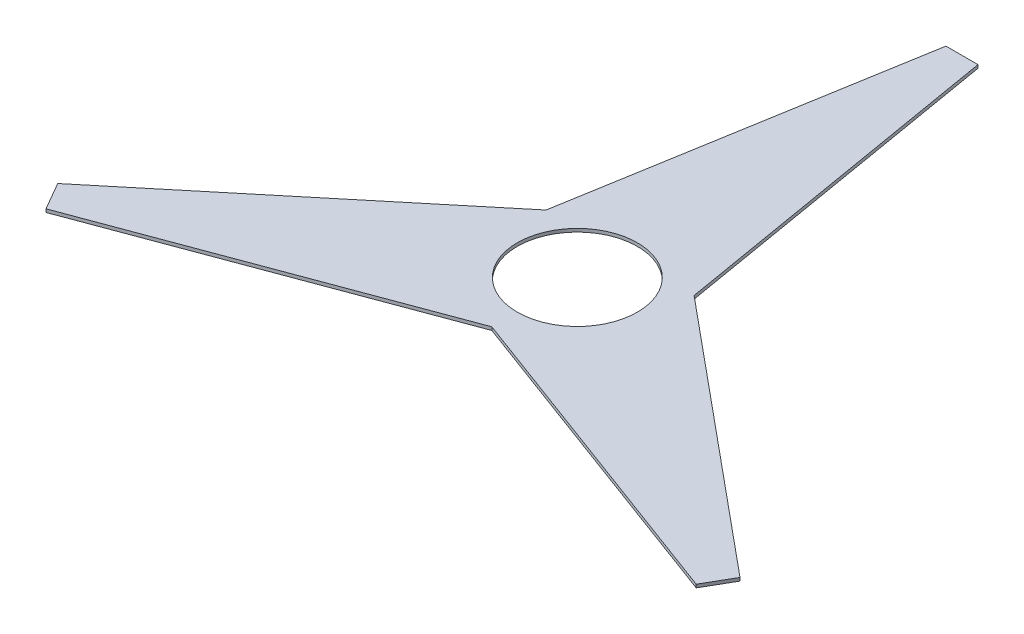
SolidWorks part; units mm, degrees
ref_plane "Alzado" through (0, 0, 0) normal (0, 0, 1) x (1, 0, 0)
ref_plane "Planta" through (0, 0, 0) normal (0, 1, 0) x (1, 0, 0)
ref_plane "Vista lateral" through (0, 0, 0) normal (1, 0, 0) x (0, 0, -1)
sketch "Croquis1" plane through (0, 0, 0) normal (0, 1, 0) x (1, 0, 0)
  line L0 (0, 0) -> (0, 1200) construction
  line L1 (1064.2305, -556.6987) -> (230.9516, 133.34)
  line L2 (1014.2305, -643.3013) -> (0, -266.68)
  line L6 (-50, 1200) -> (-230.9516, 133.34)
  line L7 (50, 1200) -> (230.9516, 133.34)
  line L9 (-1014.2305, -643.3013) -> (0, -266.68)
  line L10 (-1064.2305, -556.6987) -> (-230.9516, 133.34)
  line L11 (-50, 1200) -> (50, 1200)
  line L12 (1064.2305, -556.6987) -> (1014.2305, -643.3013)
  line L13 (-1064.2305, -556.6987) -> (-1014.2305, -643.3013)
  circle A0 centre (0, 0) radius 1250 construction
  point P17 (0, 0)
  point P20 (0, 1200)
  dimension "D1" = 2500
  dimension "D2" = 3
extrude "Saliente-Extruir2" add sketch "Croquis1" along normal blind 10
sketch "Croquis2" plane through (0, 10, 0) normal (0, 1, 0) x (1, 0, 0)
  circle A0 centre (0, 0) radius 187.5
  dimension "D1" = 375
extrude "Cortar-Extruir1" cut sketch "Croquis2" against normal blind 10
sketch "Croquis3" plane through (0, 10, 0) normal (0, 1, 0) x (1, 0, 0)
  line L0 (-50, 1200) -> (-85.7035, 989.5379)
  line L1 (-50, 1200) -> (-230.9516, 133.34) construction
  line L2 (-85.7035, 989.5379) -> (85.7035, 989.5379)
  line L3 (230.9516, 133.34) -> (50, 1200) construction
  line L4 (85.7035, 989.5379) -> (50, 1200)
  line L5 (50, 1200) -> (-50, 1200)
  line L6 (0, 1200) -> (0, 989.5379) construction
